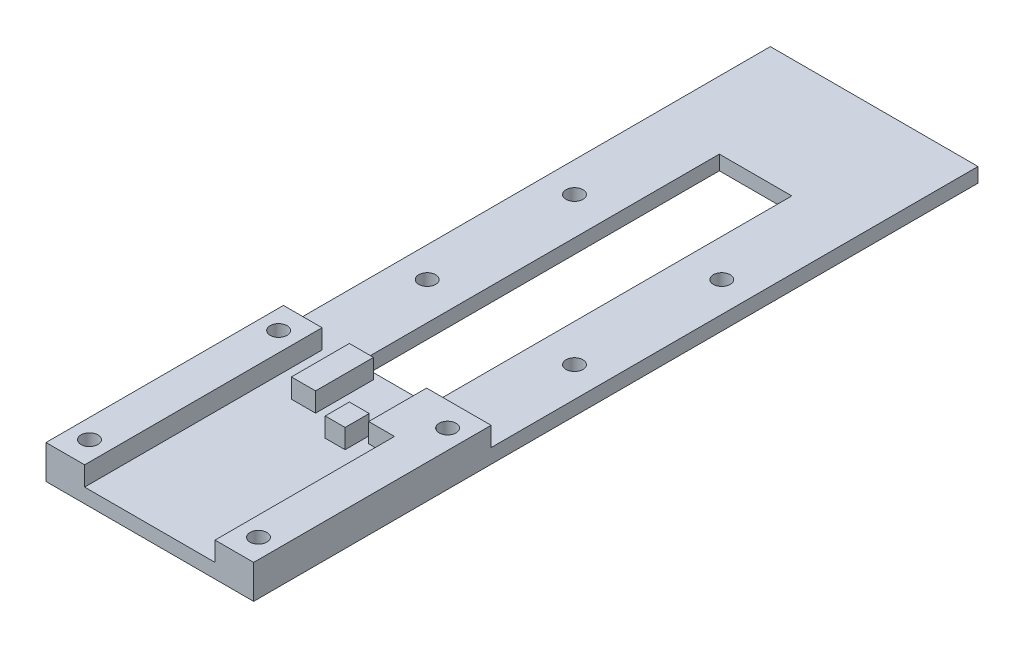
SolidWorks part; units mm, degrees
ref_plane "Front Plane" through (0, 0, 0) normal (0, 0, 1) x (1, 0, 0)
ref_plane "Top Plane" through (0, 0, 0) normal (0, 1, 0) x (1, 0, 0)
ref_plane "Right Plane" through (0, 0, 0) normal (1, 0, 0) x (0, 0, -1)
sketch "Sketch1" plane through (0, 0, 0) normal (0, 1, 0) x (1, 0, 0)
  line L1 (21.5, -75) -> (-21.5, -75)
  line L2 (21.5, -75) -> (21.5, 75)
  line L3 (21.5, 75) -> (-21.5, 75)
  line L4 (-21.5, -75) -> (-21.5, 75)
  line L5 (21.5, -75) -> (-21.5, 75) construction
  line L6 (21.5, 75) -> (-21.5, -75) construction
  point P0 (0, 0)
  dimension "D1" = 150
  dimension "D2" = 43
extrude "Boss-Extrude1" add sketch "Sketch1" along normal blind 3
sketch "Sketch2" plane through (0, 3, 0) normal (0, 1, 0) x (1, 0, 0)
  line L0 (0, 75) -> (0, 38.94) construction
  line L1 (21.5, 75) -> (-21.5, 75) construction
  line L2 (0, 75) -> (15.25, 75) construction
  line L3 (15.25, 75) -> (15.25, 28.19) construction
  line L5 (15.25, 28.19) -> (-15.25, 28.19) construction
  line L6 (15.25, 28.19) -> (15.25, -2.31) construction
  line L7 (15.25, -2.31) -> (-15.25, -2.31) construction
  line L8 (-15.25, 28.19) -> (-15.25, -2.31) construction
  circle A0 centre (15.25, 28.19) radius 1.75
  circle A1 centre (-15.25, 28.19) radius 1.75
  circle A2 centre (-15.25, -2.31) radius 1.75
  circle A3 centre (15.25, -2.31) radius 1.75
  dimension "D6" = 3.5
  dimension "D7" = 3.5
  dimension "D8" = 3.5
  dimension "D9" = 3.5
  dimension "D1" = 36.06
  dimension "D2" = 15.25
  dimension "D3" = 46.81
  dimension "D4" = 30.5
  dimension "D5" = 30.5
extrude "Cut-Extrude1" cut sketch "Sketch2" against normal blind 10
sketch "Sketch3" plane through (0, 3, 0) normal (0, 1, 0) x (1, 0, 0)
  line L0 (-15.25, 28.19) -> (15.25, -2.31) construction
  line L1 (-15.25, 28.19) -> (15.25, 28.19) construction
  line L2 (-15.25, 28.19) -> (-15.25, -2.31) construction
  line L3 (-15.25, -2.31) -> (15.25, -2.31) construction
  line L4 (15.25, 28.19) -> (15.25, -2.31) construction
  line L6 (7.5, 50.44) -> (-7.5, 50.44)
  line L7 (7.5, 50.44) -> (7.5, -24.56)
  line L8 (7.5, -24.56) -> (-7.5, -24.56)
  line L9 (-7.5, 50.44) -> (-7.5, -24.56)
  line L10 (7.5, 50.44) -> (-7.5, -24.56) construction
  line L11 (7.5, -24.56) -> (-7.5, 50.44) construction
  point P6 (0, 12.94)
  dimension "D1" = 75
  dimension "D2" = 15
extrude "Cut-Extrude2" cut sketch "Sketch3" against normal blind 10
sketch "Sketch4" plane through (0, 3, 0) normal (0, 1, 0) x (1, 0, 0)
  line L0 (0, -24.56) -> (2.65, -24.56) construction
  line L1 (-7.5, -24.56) -> (7.5, -24.56) construction
  line L2 (2.65, -24.56) -> (2.65, -25.83) construction
  line L3 (8.15, -25.83) -> (-2.85, -25.83) construction
  line L4 (8.15, -37.83) -> (-2.85, -37.83) construction
  line L5 (-2.85, -25.83) -> (-7.85, -25.83)
  line L6 (-2.85, -25.83) -> (-2.85, -37.83)
  line L7 (-2.85, -37.83) -> (-7.85, -37.83)
  line L8 (-7.85, -25.83) -> (-7.85, -37.83)
  line L9 (8.15, -25.83) -> (13.15, -25.83)
  line L10 (8.15, -25.83) -> (8.15, -37.83)
  line L11 (8.15, -37.83) -> (13.15, -37.83)
  line L12 (13.15, -25.83) -> (13.15, -37.83)
  line L14 (2.65, -37.83) -> (6.7668, -37.83)
  line L15 (2.65, -37.83) -> (2.65, -36.33)
  line L16 (2.65, -36.33) -> (6.7668, -36.33)
  line L17 (6.7668, -37.83) -> (6.7668, -36.33)
  line L18 (2.65, -37.83) -> (6.7668, -37.83)
  line L19 (2.65, -37.83) -> (2.65, -41.33)
  line L20 (2.65, -41.33) -> (6.7668, -41.33)
  line L21 (6.7668, -37.83) -> (6.7668, -41.33)
  point P8 (2.65, -25.83)
  dimension "D1" = 2.65
  dimension "D2" = 1.27
  dimension "D3" = 11
  dimension "D4" = 5
  dimension "D5" = 5
  dimension "D6" = 12
  dimension "D7" = 12
  dimension "D8" = 1.5
  dimension "D9" = 3.5
extrude "Boss-Extrude2" add sketch "Sketch4" along normal blind 4 contours L6 L5 L8 L7 | L10 L9 L12 L11 | L19 L18 L21 L20 | L15 L14 L17 L16
sketch "Sketch5" plane through (0, 3, 0) normal (0, 1, 0) x (1, 0, 0)
  line L0 (-7.85, -25.83) -> (-21.5, -25.83) construction
  line L1 (-21.5, 75) -> (-21.5, -75) construction
  line L2 (13.15, -25.83) -> (21.5, -25.83) construction
  line L3 (21.5, -75) -> (21.5, 75) construction
  line L4 (-21.5, -75) -> (21.5, -75) construction
  line L5 (-21.5, -25.83) -> (-13.5, -25.83)
  line L6 (-21.5, -25.83) -> (-21.5, -75)
  line L7 (-21.5, -75) -> (-13.5, -75)
  line L8 (-13.5, -25.83) -> (-13.5, -75)
  line L10 (21.5, -25.83) -> (13.5, -25.83)
  line L11 (21.5, -25.83) -> (21.5, -75)
  line L12 (21.5, -75) -> (13.5, -75)
  line L13 (13.5, -25.83) -> (13.5, -75)
  dimension "D1" = 8
  dimension "D2" = 8
extrude "Boss-Extrude3" add sketch "Sketch5" along normal blind 4
sketch "Sketch7" plane through (0, 3, 0) normal (0, 1, 0) x (1, 0, 0)
  line L1 (13.15, -37.83) -> (13.5, -37.83)
  line L2 (13.15, -37.83) -> (13.15, -25.83)
  line L3 (13.15, -25.83) -> (13.5, -25.83)
  line L4 (13.5, -37.83) -> (13.5, -25.83)
extrude "Boss-Extrude4" add sketch "Sketch7" along normal blind 4
sketch "Sketch8" plane through (0, 7, 0) normal (0, 1, 0) x (1, 0, 0)
  line L0 (21.5, -75) -> (17.5, -75) construction
  line L1 (13.5, -75) -> (21.5, -75) construction
  line L2 (17.5, -75) -> (17.5, -70) construction
  line L3 (21.5, -25.83) -> (-21.5, -25.83) construction
  line L4 (0, -25.83) -> (0, -75) construction
  line L5 (-13.5, -75) -> (13.5, -75) construction
  line L6 (21.5, -50.415) -> (-21.5, -50.415) construction
  line L7 (21.5, -75) -> (21.5, -25.83) construction
  line L8 (-21.5, -25.83) -> (-21.5, -75) construction
  circle A0 centre (17.5, -70) radius 1.75
  circle A1 centre (17.5, -30.83) radius 1.75
  circle A2 centre (-17.5, -70) radius 1.75
  circle A3 centre (-17.5, -30.83) radius 1.75
  dimension "D2" = 3.5
  dimension "D1" = 5
extrude "Cut-Extrude3" cut sketch "Sketch8" against normal through all
